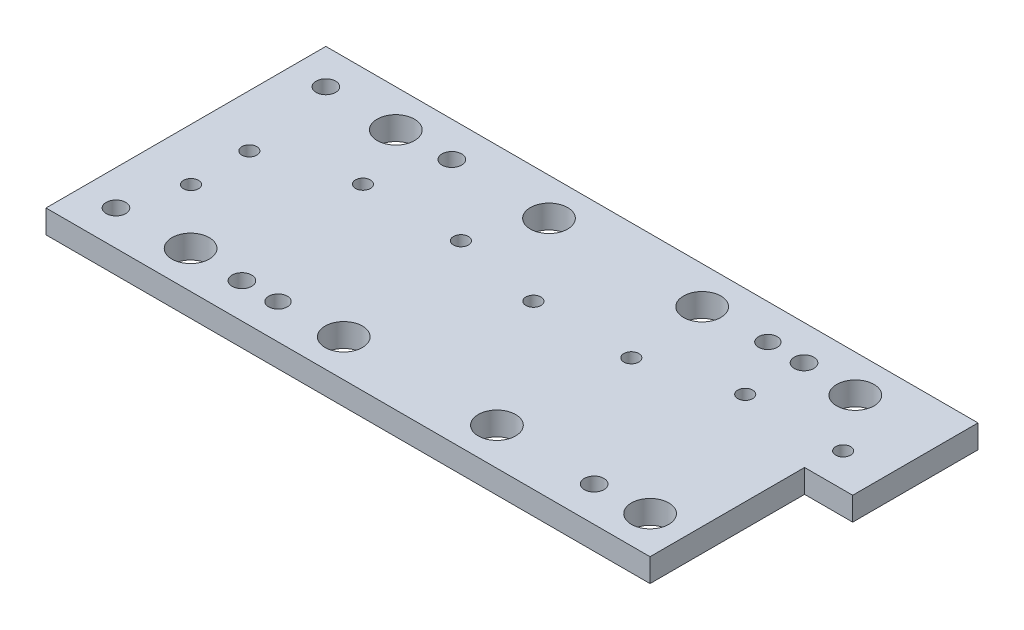
SolidWorks part; units mm, degrees
material "K110"
ref_plane "Front Plane" through (0, 0, 0) normal (0, 0, 1) x (1, 0, 0)
ref_plane "Top Plane" through (0, 0, 0) normal (0, 1, 0) x (1, 0, 0)
ref_plane "Right Plane" through (0, 0, 0) normal (1, 0, 0) x (0, 0, -1)
sketch "Sketch1" plane through (0, 0, 0) normal (0, 1, 0) x (1, 0, 0)
  line L0 (-229, 60) -> (-229, -60) construction
  line L1 (-229, -60) -> (0, -60)
  line L2 (-229, -60) -> (-229, 60)
  line L3 (-229, 60) -> (0, 60)
  line L4 (0, -60) -> (0, 60)
  point P4 (0, 0)
  dimension "D1" = 120
extrude "Boss-Extrude1" add sketch "Sketch1" along normal mid plane 10
sketch "Sketch4" plane through (0, 5, 0) normal (0, 1, 0) x (1, 0, 0)
  line L1 (0, 60) -> (20.6325, 60)
  line L2 (0, 60) -> (0, 6.27)
  line L3 (0, 6.27) -> (20.6325, 6.27)
  line L4 (20.6325, 60) -> (20.6325, 6.27)
extrude "Boss-Extrude2" add sketch "Sketch4" against normal up to surface (10 mm away) up to face at (-114.5, -5, 0)
hole_wizard "Ø16.0 (16) Diameter Hole1" positions "Sketch7" profile "Sketch6" hole size "Ø16.0" standard "ISO" end condition through all
sketch "Sketch7" plane through (0, 5, 0) normal (0, 1, 0) x (1, 0, 0)
  point P0 (-213, 44)
  point P3 (-147.323, 44)
  point P6 (-81.646, 44)
  point P9 (-15.969, 44)
  point P12 (-213, -44)
  point P15 (-147.323, -44)
  point P18 (-81.646, -44)
  point P21 (-15.969, -44)
sketch "Sketch6" plane through (-213, 5, -44) normal (1, 0, 0) x (0, 0, 1)
  line L0 (0, 0) -> (0, 10)
  line L1 (0, 10) -> (8, 10)
  line L2 (8, 10) -> (8, 0)
  line L5 (8, 0) -> (0, 0)
  line L11 (0, -6.35) -> (0, 107.95) construction
  dimension "Thru Hole Dia." = 16
  dimension "Thru Hole Depth" = 10
hole_wizard "M6 Clearance Hole1" positions "Sketch12" profile "Sketch11" hole size "M6" standard "ISO" end condition through all
sketch "Sketch12" plane through (0, 5, 0) normal (0, 1, 0) x (1, 0, 0)
  point P0 (-199.875, 16.78)
  point P3 (-157.875, 16.78)
  point P6 (-119.875, 9.8524)
  point P9 (-77.875, 9.8524)
  point P12 (-39.875, 20.691)
  point P15 (2.125, 20.691)
sketch "Sketch11" plane through (-199.875, 5, -16.78) normal (1, 0, 0) x (0, 0, 1)
  line L0 (0, 0) -> (0, 10)
  line L1 (0, 10) -> (3.2, 10)
  line L2 (3.2, 10) -> (3.2, 0)
  line L5 (3.2, 0) -> (0, 0)
  line L11 (0, -6.35) -> (0, 107.95) construction
  dimension "Thru Hole Dia." = 6.4
  dimension "Thru Hole Depth" = 10
hole_wizard "M8 Clearance Hole1" positions "Sketch15" profile "Sketch14" hole size "M8" standard "ISO" end condition through all
sketch "Sketch15" plane through (0, 5, 0) normal (0, 1, 0) x (1, 0, 0)
  point P0 (-190, -45)
  point P3 (-38.969, -45)
  point P6 (-38.969, 45)
  point P9 (-190, 45)
sketch "Sketch14" plane through (-190, 5, 45) normal (1, 0, 0) x (0, 0, 1)
  line L0 (0, 0) -> (0, 10)
  line L1 (0, 10) -> (4.2, 10)
  line L2 (4.2, 10) -> (4.2, 0)
  line L5 (4.2, 0) -> (0, 0)
  line L11 (0, -6.35) -> (0, 107.95) construction
  dimension "Thru Hole Dia." = 8.4
  dimension "Thru Hole Depth" = 10
hole_wizard "Ø8.0mm Dowel Hole1" positions "Sketch18" profile "Sketch17" hole size "Ø8.0" standard "ISO" end condition through all
sketch "Sketch18" plane through (0, 5, 0) normal (0, 1, 0) x (1, 0, 0)
  point P0 (-54.469, 45)
  point P3 (-174.5, -45)
sketch "Sketch17" plane through (-54.469, 5, -45) normal (1, 0, 0) x (0, 0, 1)
  line L0 (0, 0) -> (0, 10)
  line L1 (0, 10) -> (4, 10)
  line L2 (4, 10) -> (4, 0)
  line L5 (4, 0) -> (0, 0)
  line L11 (0, -6.35) -> (0, 107.95) construction
  dimension "Thru Hole Dia." = 8
  dimension "Thru Hole Depth" = 10
sketch "Sketch20" plane through (-229, 0, 0) normal (-1, 0, 0) x (0, 0, 1)
  line L4 (-60, -5) -> (60, -5)
  line L5 (60, -5) -> (60, 5)
  line L6 (60, 5) -> (-60, 5)
  line L7 (-60, 5) -> (-60, -5)
  line L8 (-60, -5) -> (60, -5)
  line L9 (60, -5) -> (60, 5)
  line L10 (60, 5) -> (-60, 5)
  line L11 (-60, 5) -> (-60, -5)
  dimension "D1" = 0
extrude "Boss-Extrude3" add sketch "Sketch20" along normal blind 30
hole_wizard "M8 Clearance Hole2" positions "Sketch26" profile "Sketch24" hole size "M8" standard "ISO" end condition through all
sketch "Sketch26" plane through (0, 5, 0) normal (0, 1, 0) x (1, 0, 0)
  point P11 (-244, -45)
  point P14 (-244, 45)
sketch "Sketch24" plane through (-244, 5, 45) normal (1, 0, 0) x (0, 0, 1)
  line L0 (0, 0) -> (0, 10)
  line L1 (0, 10) -> (4.2, 10)
  line L2 (4.2, 10) -> (4.2, 0)
  line L5 (4.2, 0) -> (0, 0)
  line L11 (0, -6.35) -> (0, 107.95) construction
  dimension "Thru Hole Dia." = 8.4
  dimension "Thru Hole Depth" = 10
hole_wizard "M6 Clearance Hole2" positions "Sketch29" profile "Sketch28" hole size "M6" standard "ISO" end condition through all
sketch "Sketch29" plane through (0, 5, 0) normal (0, 1, 0) x (1, 0, 0)
  point P0 (-236.6, -20.22)
  point P3 (-236.6, 4.78)
sketch "Sketch28" plane through (-236.6, 5, 20.22) normal (1, 0, 0) x (0, 0, 1)
  line L0 (0, 0) -> (0, 10)
  line L1 (0, 10) -> (3.2, 10)
  line L2 (3.2, 10) -> (3.2, 0)
  line L5 (3.2, 0) -> (0, 0)
  line L11 (0, -6.35) -> (0, 107.95) construction
  dimension "Thru Hole Dia." = 6.4
  dimension "Thru Hole Depth" = 10
